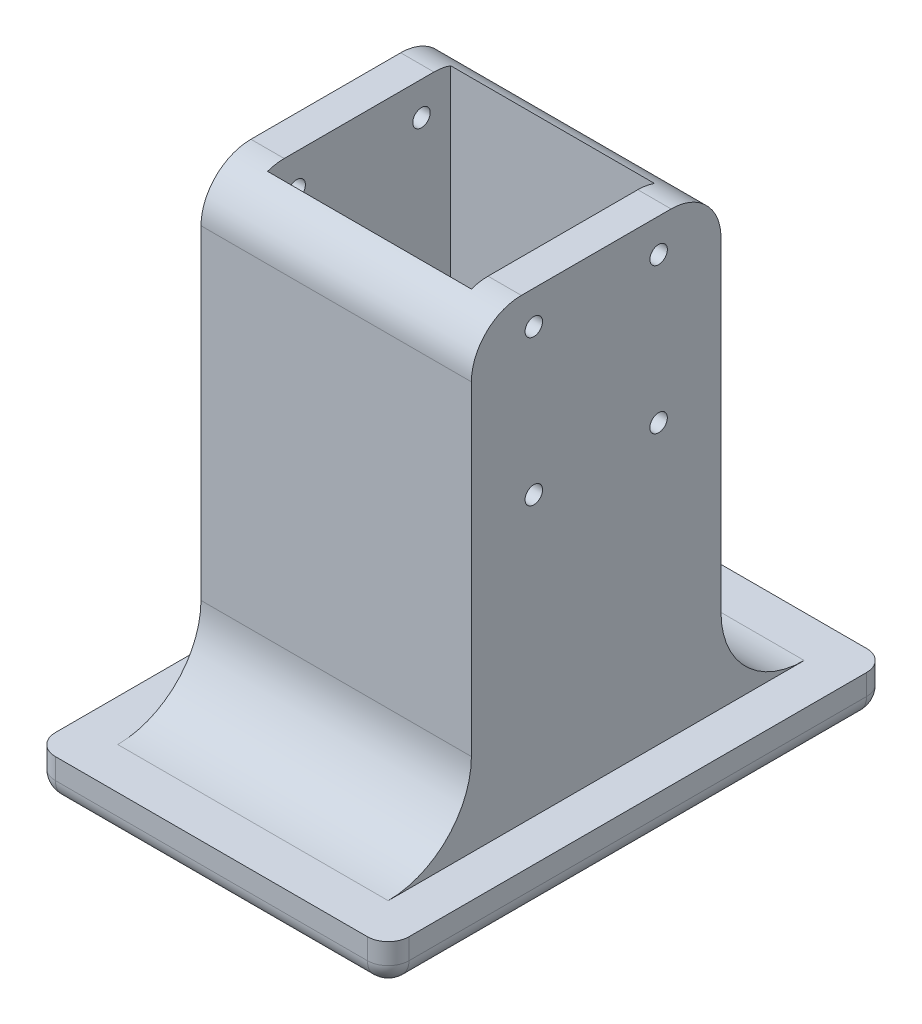
SolidWorks part; units mm, degrees
ref_plane "前视基准面" through (0, 0, 0) normal (0, 0, 1) x (1, 0, 0)
ref_plane "上视基准面" through (0, 0, 0) normal (0, 1, 0) x (1, 0, 0)
ref_plane "右视基准面" through (0, 0, 0) normal (1, 0, 0) x (0, 0, -1)
other "Configuration Table"
sketch "草图1" plane through (0, 0, 0) normal (0, 1, 0) x (1, 0, 0)
  line L1 (42.5, -60) -> (-42.5, -60)
  line L2 (42.5, -60) -> (42.5, 60)
  line L3 (42.5, 60) -> (-42.5, 60)
  line L4 (-42.5, -60) -> (-42.5, 60)
  line L5 (42.5, -60) -> (-42.5, 60) construction
  line L6 (42.5, 60) -> (-42.5, -60) construction
  point P0 (0, 0)
  dimension "D1" = 85
  dimension "D2" = 120
extrude "凸台-拉伸1" add sketch "草图1" along normal blind 10
sketch "草图2" plane through (0, 10, 0) normal (0, 1, 0) x (1, 0, 0)
  line L1 (32.5, -30) -> (-32.5, -30)
  line L2 (32.5, -30) -> (32.5, 30)
  line L3 (32.5, 30) -> (-32.5, 30)
  line L4 (-32.5, -30) -> (-32.5, 30)
  line L5 (32.5, -30) -> (-32.5, 30) construction
  line L6 (32.5, 30) -> (-32.5, -30) construction
  line L9 (24.5, -22) -> (-24.5, -22)
  line L10 (24.5, -22) -> (24.5, 22)
  line L11 (24.5, 22) -> (-24.5, 22)
  line L12 (-24.5, -22) -> (-24.5, 22)
  line L13 (24.5, -22) -> (-24.5, 22) construction
  line L14 (24.5, 22) -> (-24.5, -22) construction
  point P0 (0, 0)
  point P10 (0, 0)
  dimension "D1" = 60
  dimension "D2" = 8
  dimension "D3" = 8
  dimension "D4" = 65
extrude "凸台-拉伸2" add sketch "草图2" along normal blind 110
fillet "圆角1" radius 5 8 edges at (0, 0, 60) (42.5, 0, 0) (0, 0, -60) (-42.5, 0, 0) (42.5, 5, 60) (-42.5, 5, 60) (-42.5, 5, -60) (42.5, 5, -60)
fillet "圆角2" radius 12 2 edges at (0, 120, 30) (0, 120, -30)
sketch "草图3" plane through (42.5, 0, 0) normal (1, 0, 0) x (0, 0, -1)
  line L1 (15, 77) -> (-15, 77) construction
  line L2 (15, 77) -> (15, 112) construction
  line L3 (15, 112) -> (-15, 112) construction
  line L4 (-15, 77) -> (-15, 112) construction
  line L5 (15, 77) -> (-15, 112) construction
  line L6 (15, 112) -> (-15, 77) construction
  line L7 (-30, 108) -> (-30, 10) construction
  line L9 (0, 112) -> (0, 77) construction
  line L10 (15, 94.5) -> (-15, 94.5) construction
  line L11 (30, 108) -> (30, 10) construction
  line L12 (-18, 120) -> (18, 120) construction
  circle A0 centre (-15, 112) radius 2.1
  circle A1 centre (15, 112) radius 2.1
  circle A2 centre (15, 77) radius 2.1
  circle A3 centre (-15, 77) radius 2.1
  point P0 (0, 94.5)
  dimension "D5" = 4.2
  dimension "D1" = 8
  dimension "D2" = 15
  dimension "D3" = 15
  dimension "D4" = 35
extrude "切除-拉伸1" cut sketch "草图3" against normal through all
fillet "圆角3" radius 20 2 edges at (0, 10, -30) (0, 10, 30)
